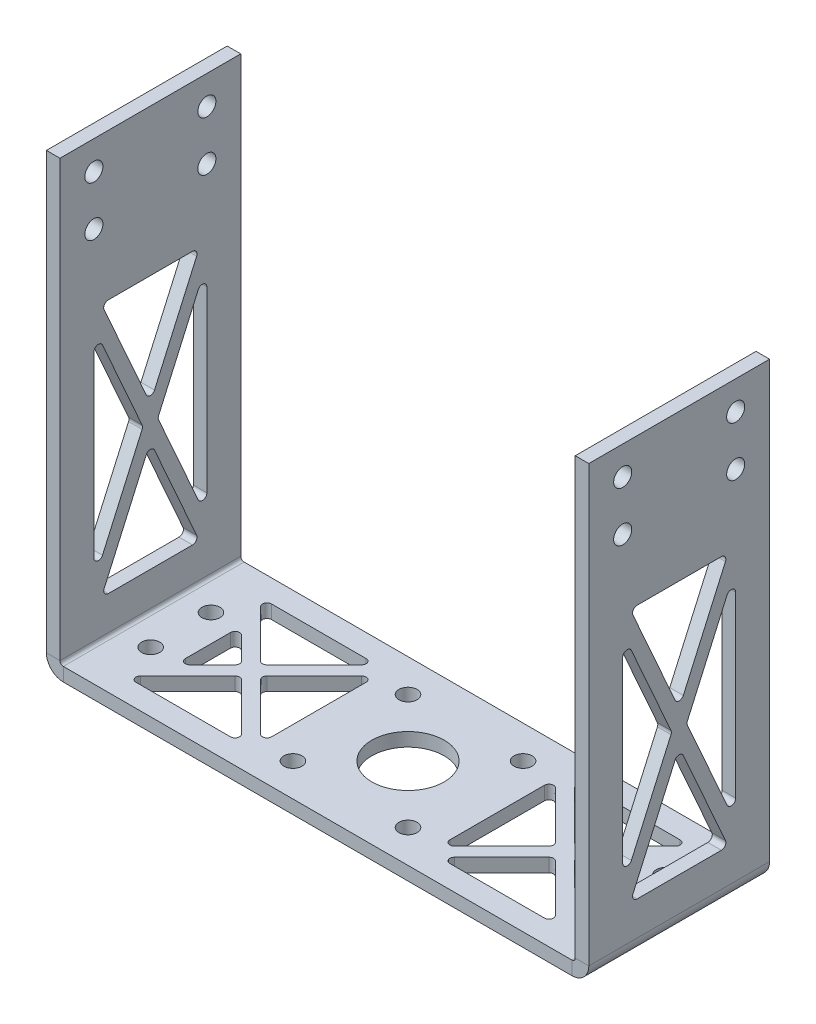
SolidWorks part; units mm, degrees
note: The reader was unsure of these and kept them because the rebuilt part matched: flange length of "Edge-Flange1", "Edge-Flange2".
material "Alloy Steel (SS)"
ref_plane "Front Plane" through (0, 0, 0) normal (0, 0, 1) x (1, 0, 0)
ref_plane "Top Plane" through (0, 0, 0) normal (0, 1, 0) x (1, 0, 0)
ref_plane "Right Plane" through (0, 0, 0) normal (1, 0, 0) x (0, 0, -1)
sketch "Sketch3" plane through (0, 0, 0) normal (0, 1, 0) x (1, 0, 0)
  line L6 (-57, 20) -> (57, 20)
  line L18 (-57, 20) -> (-57, -20)
  line L19 (-57, -20) -> (57, -20)
  line L20 (57, 20) -> (57, -20)
  line L21 (-57, 20) -> (57, -20) construction
  line L22 (-57, -20) -> (57, 20) construction
  point P0 (0, 0)
  dimension "D1" = 40
  dimension "D2" = 114
base flange "Base-Flange1" sketch "Sketch3" thickness 3 reverse thickness direction no parameters "D1"=0.7366
edge flange "Edge-Flange1" sketch "Sketch7" flange angle 90 flange length 100 flange position material outside bend radius 0.7366 thickness 3 relief rectangular parameters "D6"=10
sketch "Sketch7" plane through (-57, 0, 0) normal (-1, 0, 0) x (0, 0, 1)
  line L0 (-20, 0) -> (20, 0) construction
  line L1 (-20, 0) -> (20, 0)
  line L2 (-20, 0) -> (-20, 97)
  line L3 (-20, 97) -> (20, 97)
  line L4 (20, 97) -> (20, 0)
bend "EdgeBend1" bend radius 0.7366 bend angle 90 parameters "D5"=1
edge flange "Edge-Flange2" sketch "Sketch10" flange angle 90 flange length 100 flange position material outside bend radius 0.7366 thickness 3 relief rectangular parameters "D6"=10
sketch "Sketch10" plane through (57, 0, 0) normal (1, 0, 0) x (0, 0, -1)
  line L0 (-20, 0) -> (20, 0) construction
  line L1 (-20, 0) -> (20, 0)
  line L2 (-20, 0) -> (-20, 97)
  line L3 (-20, 97) -> (20, 97)
  line L4 (20, 97) -> (20, 0)
bend "EdgeBend2" bend radius 0.7366 bend angle 90 parameters "D5"=2
sketch "Sketch11" plane through (0, -3, 0) normal (0, -1, 0) x (-1, 0, 0)
  line L0 (-56.2634, 20) -> (56.2634, -20) construction
  line L1 (56.2634, 20) -> (-56.2634, -20) construction
  line L2 (12.7279, 12.7279) -> (12.7279, 20) construction
  line L3 (-56.2634, 20) -> (56.2634, 20) construction
  line L4 (-50.2634, -20) -> (-50.2634, -6.6667) construction
  line L5 (56.2634, -20) -> (-56.2634, -20) construction
  line L6 (-50.2634, -6.6667) -> (-50.2634, 6.6667) construction
  line L7 (-50.2634, 6.6667) -> (-50.2634, 20) construction
  line L8 (50.2634, -20) -> (50.2634, -6.6667) construction
  line L9 (50.2634, -6.6667) -> (50.2634, 6.6667) construction
  line L10 (50.2634, 6.6667) -> (50.2634, 20) construction
  line L11 (50.2634, 0) -> (56.2634, 0) construction
  line L12 (56.2634, -20) -> (56.2634, 20) construction
  line L13 (-50.2634, 0) -> (-56.2634, 0) construction
  line L14 (-56.2634, 20) -> (-56.2634, -20) construction
  line L16 (-56.2634, 20) -> (56.2634, 20) construction
  line L17 (-12.7279, 12.7279) -> (-12.7279, 20) construction
  circle A0 centre (0, 0) radius 8
  circle A1 centre (12.7279, 12.7279) radius 2
  circle A2 centre (12.7279, -12.7279) radius 2
  circle A3 centre (-12.7279, -12.7279) radius 2
  circle A4 centre (-12.7279, 12.7279) radius 2
  circle A5 centre (50.2634, 6.6667) radius 2
  circle A6 centre (-50.2634, 6.6667) radius 2
  circle A7 centre (50.2634, -6.6667) radius 2
  circle A8 centre (-50.2634, -6.6667) radius 2
  point P29 (0, 0)
  point P47 (12.24, 12.24)
  dimension "D1" = 16
  dimension "D2" = 4
  dimension "D4" = 6
  dimension "D5" = 18
  dimension "D3" = 4
extrude "Cut-Extrude1" cut sketch "Sketch11" against normal blind 10 normal cut yes
sketch "Sketch12" plane through (60, 0, 0) normal (1, 0, 0) x (0, 0, -1)
  circle A0 centre (12.5, 79.6742) radius 2
  circle A1 centre (12.5, 90.6742) radius 2
  circle A2 centre (-12.5, 79.6742) radius 2
  circle A3 centre (-12.5, 90.6742) radius 2
  dimension "D1" = 4
  dimension "D2" = 4
  dimension "D3" = 4
  dimension "D4" = 4
extrude "Cut-Extrude2" cut sketch "Sketch12" against normal up to surface (120 mm away) normal cut yes up to face at (-60, 48.8683, 0)
sketch "Sketch14" plane through (60, 0, 0) normal (1, 0, 0) x (0, 0, -1)
  line L0 (-12.5, 64.5) -> (12.5, 8.2366) construction
  line L5 (-12.5, 60.8059) -> (-1.6414, 36.3683)
  line L6 (-12.5, 8.2366) -> (12.5, 64.5) construction
  line L7 (-12.5, 72) -> (-12.5, 64.5) construction
  line L32 (-17, 72) -> (-8, 72) construction
  line L33 (-12.5, 64.5) -> (-20, 64.5) construction
  line L34 (-20, 97) -> (-20, 0.7366) construction
  line L35 (12.5, 72) -> (12.5, 64.5) construction
  line L36 (8, 72) -> (17, 72) construction
  line L37 (12.5, 64.5) -> (20, 64.5) construction
  line L38 (20, 0.7366) -> (20, 97) construction
  line L39 (12.5, 0.7366) -> (12.5, 8.2366) construction
  line L40 (20, 0.7366) -> (-20, 0.7366) construction
  line L41 (12.5, 8.2366) -> (20, 8.2366) construction
  line L42 (-12.5, 0.7366) -> (-12.5, 8.2366) construction
  line L43 (-12.5, 8.2366) -> (-20, 8.2366) construction
  line L44 (-1.6414, 36.3683) -> (-12.5, 11.9307)
  line L45 (-12.5, 11.9307) -> (-12.5, 60.8059)
  line L46 (-10.8586, 64.5) -> (0, 40.0624)
  line L47 (0, 40.0624) -> (10.8586, 64.5)
  line L48 (10.8586, 64.5) -> (-10.8586, 64.5)
  line L49 (12.5, 60.8059) -> (1.6414, 36.3683)
  line L50 (1.6414, 36.3683) -> (12.5, 11.9307)
  line L51 (12.5, 11.9307) -> (12.5, 60.8059)
  line L52 (10.8586, 8.2366) -> (0, 32.6742)
  line L53 (0, 32.6742) -> (-10.8586, 8.2366)
  line L54 (-10.8586, 8.2366) -> (10.8586, 8.2366)
  line L55 (-8.6204, 52.0747) -> (-7.2496, 52.6838) construction
  line L56 (-4.4648, 50.1105) -> (-5.8356, 49.5014) construction
  line L57 (8.9336, 52.7797) -> (7.5629, 53.3888) construction
  line L58 (4.7494, 50.7511) -> (6.1202, 50.1421) construction
  line L59 (7.3086, 16.2261) -> (8.6793, 16.8352) construction
  line L60 (6.7233, 24.9312) -> (5.3526, 24.3222) construction
  line L61 (-6.4395, 25.5699) -> (-5.0688, 24.9609) construction
  line L62 (-7.2868, 16.275) -> (-8.6576, 16.8841) construction
  dimension "D1" = 1.5
extrude "Cut-Extrude3" cut sketch "Sketch14" against normal through all both and the other way through all normal cut yes
sketch "Sketch15" plane through (0, -3, 0) normal (0, -1, 0) x (1, 0, 0)
  line L0 (44.2634, -9.5355) -> (19.7279, 15) construction
  line L1 (19.7279, 15) -> (19.7279, -15) construction
  line L2 (19.7279, -15) -> (44.2634, 9.5355) construction
  line L3 (44.2634, 9.5355) -> (44.2634, -9.5355) construction
  line L4 (44.2634, -9.5355) -> (44.2634, -20) construction
  line L5 (56.2634, -20) -> (-56.2634, -20) construction
  line L6 (44.2634, -9.5355) -> (56.2634, -9.5355) construction
  line L7 (56.2634, -20) -> (56.2634, 20) construction
  line L8 (44.2634, 9.5355) -> (56.2634, 9.5355) construction
  line L9 (44.2634, 9.5355) -> (44.2634, 20) construction
  line L10 (-56.2634, 20) -> (56.2634, 20) construction
  line L11 (19.7279, 15) -> (19.7279, 20) construction
  line L12 (19.7279, -15) -> (19.7279, -20) construction
  line L13 (14.7279, 20) -> (14.7279, -20) construction
  line L14 (19.7279, 15) -> (14.7279, 15) construction
  line L15 (19.7279, -15) -> (14.7279, -15) construction
  line L16 (19.7279, 12.8787) -> (32.6066, 0)
  line L17 (32.6066, 0) -> (19.7279, -12.8787)
  line L18 (19.7279, -12.8787) -> (19.7279, 12.8787)
  line L19 (21.8492, 15) -> (34.7279, 2.1213)
  line L20 (34.7279, 2.1213) -> (47.6066, 15)
  line L21 (47.6066, 15) -> (21.8492, 15)
  line L22 (44.2634, 7.4142) -> (36.8492, 0)
  line L23 (36.8492, 0) -> (44.2634, -7.4142)
  line L24 (44.2634, -7.4142) -> (44.2634, 7.4142)
  line L25 (47.6066, -15) -> (34.7279, -2.1213)
  line L26 (34.7279, -2.1213) -> (21.8492, -15)
  line L27 (21.8492, -15) -> (47.6066, -15)
  line L28 (23.339, 9.2676) -> (24.3996, 10.3283) construction
  line L29 (29.0016, 7.8476) -> (27.941, 6.7869) construction
  line L30 (39.7139, 7.1073) -> (40.7746, 6.0467) construction
  line L31 (44.7198, 7.8705) -> (43.6591, 8.9312) construction
  line L32 (42.3126, -9.706) -> (43.3732, -8.6453) construction
  line L33 (41.7745, -4.9253) -> (40.7139, -5.9859) construction
  line L34 (27.2243, -5.3823) -> (28.285, -6.4429) construction
  line L35 (25.3932, -9.3348) -> (26.4538, -10.3954) construction
  line L36 (0, 12.7279) -> (0, -12.7279) construction
  line L37 (-25.3932, -9.3348) -> (-26.4538, -10.3954) construction
  line L38 (-27.2243, -5.3823) -> (-28.285, -6.4429) construction
  line L39 (-41.7745, -4.9253) -> (-40.7139, -5.9859) construction
  line L40 (-42.3126, -9.706) -> (-43.3732, -8.6453) construction
  line L41 (-44.7198, 7.8705) -> (-43.6591, 8.9312) construction
  line L42 (-39.7139, 7.1073) -> (-40.7746, 6.0467) construction
  line L43 (-29.0016, 7.8476) -> (-27.941, 6.7869) construction
  line L44 (-23.339, 9.2676) -> (-24.3996, 10.3283) construction
  line L45 (-19.7279, -15) -> (-14.7279, -15) construction
  line L46 (-19.7279, 15) -> (-14.7279, 15) construction
  line L47 (-14.7279, 20) -> (-14.7279, -20) construction
  line L48 (-19.7279, -15) -> (-19.7279, -20) construction
  line L49 (-19.7279, 15) -> (-19.7279, 20) construction
  line L50 (-44.2634, 9.5355) -> (-44.2634, 20) construction
  line L51 (-44.2634, 9.5355) -> (-56.2634, 9.5355) construction
  line L52 (-44.2634, -9.5355) -> (-56.2634, -9.5355) construction
  line L53 (-44.2634, -9.5355) -> (-44.2634, -20) construction
  line L54 (-44.2634, 9.5355) -> (-44.2634, -9.5355) construction
  line L55 (-19.7279, -15) -> (-44.2634, 9.5355) construction
  line L56 (-19.7279, 15) -> (-19.7279, -15) construction
  line L57 (-44.2634, -9.5355) -> (-19.7279, 15) construction
  line L58 (-21.8492, -15) -> (-47.6066, -15)
  line L59 (-34.7279, -2.1213) -> (-21.8492, -15)
  line L60 (-47.6066, -15) -> (-34.7279, -2.1213)
  line L61 (-44.2634, -7.4142) -> (-44.2634, 7.4142)
  line L62 (-36.8492, 0) -> (-44.2634, -7.4142)
  line L63 (-44.2634, 7.4142) -> (-36.8492, 0)
  line L64 (-47.6066, 15) -> (-21.8492, 15)
  line L65 (-34.7279, 2.1213) -> (-47.6066, 15)
  line L66 (-21.8492, 15) -> (-34.7279, 2.1213)
  line L67 (-19.7279, -12.8787) -> (-19.7279, 12.8787)
  line L68 (-32.6066, 0) -> (-19.7279, -12.8787)
  line L69 (-19.7279, 12.8787) -> (-32.6066, 0)
  line L70 (-12.7279, -12.7279) -> (12.7279, -12.7279) construction
  line L71 (-12.7279, 12.7279) -> (12.7279, 12.7279) construction
  circle A0 centre (12.7279, -12.7279) radius 2 construction
  point P94 (0, 12.7279)
  point P97 (0, -12.7279)
  dimension "D1" = 5
  dimension "D2" = 1.5
  dimension "D3" = 12
extrude "Cut-Extrude4" cut sketch "Sketch15" against normal blind 10 normal cut yes
fillet "Fillet1" radius 1 48 edges at (-58.5, 40.0624, 0) (-58.5, 32.6742, 0) (-58.5, 64.5, 10.8586) (-58.5, 8.2366, 10.8586) (-58.5, 36.3683, -1.6414) (-58.5, 8.2366, -10.8586) (-58.5, 64.5, -10.8586) (-58.5, 36.3683, 1.6414) (58.5, 36.3683, -1.6414) (58.5, 36.3683, 1.6414) (58.5, 40.0624, 0) (58.5, 64.5, 10.8586) (58.5, 64.5, -10.8586) (58.5, 60.8059, 12.5) (58.5, 60.8059, -12.5) (58.5, 32.6742, 0) (58.5, 11.9307, -12.5) (58.5, 11.9307, 12.5) (58.5, 8.2366, 10.8586) (58.5, 8.2366, -10.8586) (19.7279, -1.5, -12.8787) (-44.2634, -1.5, -7.4142) (34.7279, -1.5, 2.1213) (-21.8492, -1.5, -15) (47.6066, -1.5, -15) (44.2634, -1.5, -7.4142) (-34.7279, -1.5, 2.1213) (-19.7279, -1.5, -12.8787) (44.2634, -1.5, 7.4142) (-19.7279, -1.5, 12.8787) (32.6066, -1.5, 0) (47.6066, -1.5, 15) (-21.8492, -1.5, 15) (-36.8492, -1.5, 0) (19.7279, -1.5, 12.8787) (34.7279, -1.5, -2.1213) (-44.2634, -1.5, 7.4142) (-34.7279, -1.5, -2.1213) (21.8492, -1.5, 15) (-47.6066, -1.5, 15) (21.8492, -1.5, -15) (36.8492, -1.5, 0) (-32.6066, -1.5, 0) (-47.6066, -1.5, -15)
sketch "Bend-Lines1" [suppressed] plane through (0, 0, 0) normal (0, 1, 0) x (1, 0, 0)
sketch "Bounding-Box1" [suppressed] plane through (0, 0, 0) normal (0, 1, 0) x (1, 0, 0)
sheet metal parameters "Sheet-Metal1" thickness 3 parameters "D1"=0.7366
flat pattern "Flat-Pattern1" [suppressed]
sketch "Bend-Lines2" plane through (0, 0, 0) normal (0, 1, 0) x (1, 0, 0)
sketch3d "Bounding-Box2" [suppressed]
  line L0 (57, -20, 0) -> (-57, -20, 0) construction
  line L1 (57, 20, 0) -> (-57, 20, 0) construction
  line L2 (57, -20, 0) -> (57, 20, 0) construction
  line L3 (-57, -20, 0) -> (-57, 20, 0) construction
sheet metal parameters "Sheet-Metal2" thickness 3 parameters "D1"=0.7366
flat pattern "Flat-Pattern1"
sketch "Bend-Lines2" plane through (0, 0, 0) normal (0, 1, 0) x (1, 0, 0)
  line L0 (-58.02, 20) -> (-58.02, -20) construction
  line L1 (-58.02, 20) -> (-58.02, -20) construction
sketch3d "Bounding-Box2" [suppressed]
  line L0 (57, -20, 0) -> (-90.7766, -20, 0) construction
  line L1 (57, 20, 0) -> (-90.7766, 20, 0) construction
  line L2 (57, -20, 0) -> (57, 20, 0) construction
  line L3 (-90.7766, -20, 0) -> (-90.7766, 20, 0) construction
bend of the flat pattern "Flatten-<EdgeBend1>1"
sheet metal parameters "Sheet-Metal3" thickness 3 parameters "D1"=0.7366
flat pattern "Flat-Pattern1"
sketch "Bend-Lines2" plane through (0, 0, 0) normal (0, 1, 0) x (1, 0, 0)
  line L0 (-58.02, 20) -> (-58.02, -20) construction
  line L1 (-58.02, 20) -> (-58.02, -20) construction
  line L2 (58.02, -20) -> (58.02, 20) construction
  line L3 (58.02, -20) -> (58.02, 20) construction
sketch3d "Bounding-Box2" [suppressed]
  line L0 (156.04, -20, 0) -> (-156.04, -20, 0) construction
  line L1 (156.04, 20, 0) -> (-156.04, 20, 0) construction
  line L2 (156.04, -20, 0) -> (156.04, 20, 0) construction
  line L3 (-156.04, -20, 0) -> (-156.04, 20, 0) construction
bend of the flat pattern "Flatten-<EdgeBend1>1"
bend of the flat pattern "Flatten-<EdgeBend2>1"
sheet metal parameters "Sheet-Metal4" thickness 3 parameters "D1"=0.7366
flat pattern "Flat-Pattern1"
sketch "Bend-Lines2" plane through (0, 0, 0) normal (0, 1, 0) x (1, 0, 0)
  line L0 (-58.02, 20) -> (-58.02, -20) construction
  line L1 (-58.02, 20) -> (-58.02, -20) construction
  line L2 (58.02, -20) -> (58.02, 20) construction
  line L3 (58.02, -20) -> (58.02, 20) construction
sketch3d "Bounding-Box2" [suppressed]
  line L0 (156.04, -20, 0) -> (-156.04, -20, 0) construction
  line L1 (156.04, 20, 0) -> (-156.04, 20, 0) construction
  line L2 (156.04, -20, 0) -> (156.04, 20, 0) construction
  line L3 (-156.04, -20, 0) -> (-156.04, 20, 0) construction
bend of the flat pattern "Flatten-<EdgeBend1>1"
bend of the flat pattern "Flatten-<EdgeBend2>1"
sheet metal parameters "Sheet-Metal5" thickness 3 parameters "D1"=0.7366
flat pattern "Flat-Pattern1"
sketch "Bend-Lines2" plane through (0, 0, 0) normal (0, 1, 0) x (1, 0, 0)
  line L0 (-58.02, 20) -> (-58.02, -20) construction
  line L1 (-58.02, 20) -> (-58.02, -20) construction
  line L2 (58.02, -20) -> (58.02, 20) construction
  line L3 (58.02, -20) -> (58.02, 20) construction
sketch3d "Bounding-Box2" [suppressed]
  line L0 (156.04, -20, 0) -> (-156.04, -20, 0) construction
  line L1 (156.04, 20, 0) -> (-156.04, 20, 0) construction
  line L2 (156.04, -20, 0) -> (156.04, 20, 0) construction
  line L3 (-156.04, -20, 0) -> (-156.04, 20, 0) construction
bend of the flat pattern "Flatten-<EdgeBend1>1"
bend of the flat pattern "Flatten-<EdgeBend2>1"
sheet metal parameters "Sheet-Metal6" thickness 3 parameters "D1"=0.7366
flat pattern "Flat-Pattern1"
sketch "Bend-Lines2" plane through (0, 0, 0) normal (0, 1, 0) x (1, 0, 0)
  line L0 (-58.02, 20) -> (-58.02, -20) construction
  line L1 (-58.02, 20) -> (-58.02, -20) construction
  line L2 (58.02, -20) -> (58.02, 20) construction
  line L3 (58.02, -20) -> (58.02, 20) construction
sketch3d "Bounding-Box2" [suppressed]
  line L0 (156.04, -20, 0) -> (-156.04, -20, 0) construction
  line L1 (156.04, 20, 0) -> (-156.04, 20, 0) construction
  line L2 (156.04, -20, 0) -> (156.04, 20, 0) construction
  line L3 (-156.04, -20, 0) -> (-156.04, 20, 0) construction
bend of the flat pattern "Flatten-<EdgeBend1>1"
bend of the flat pattern "Flatten-<EdgeBend2>1"
sheet metal parameters "Sheet-Metal7" thickness 3 parameters "D1"=0.7366
flat pattern "Flat-Pattern1"
sketch "Bend-Lines2" plane through (0, 0, 0) normal (0, 1, 0) x (1, 0, 0)
  line L0 (-58.02, 20) -> (-58.02, -20) construction
  line L1 (-58.02, 20) -> (-58.02, -20) construction
  line L2 (58.02, -20) -> (58.02, 20) construction
  line L3 (58.02, -20) -> (58.02, 20) construction
sketch3d "Bounding-Box2" [suppressed]
  line L0 (156.04, -20, 0) -> (-156.04, -20, 0) construction
  line L1 (156.04, 20, 0) -> (-156.04, 20, 0) construction
  line L2 (156.04, -20, 0) -> (156.04, 20, 0) construction
  line L3 (-156.04, -20, 0) -> (-156.04, 20, 0) construction
bend of the flat pattern "Flatten-<EdgeBend1>1"
bend of the flat pattern "Flatten-<EdgeBend2>1"
